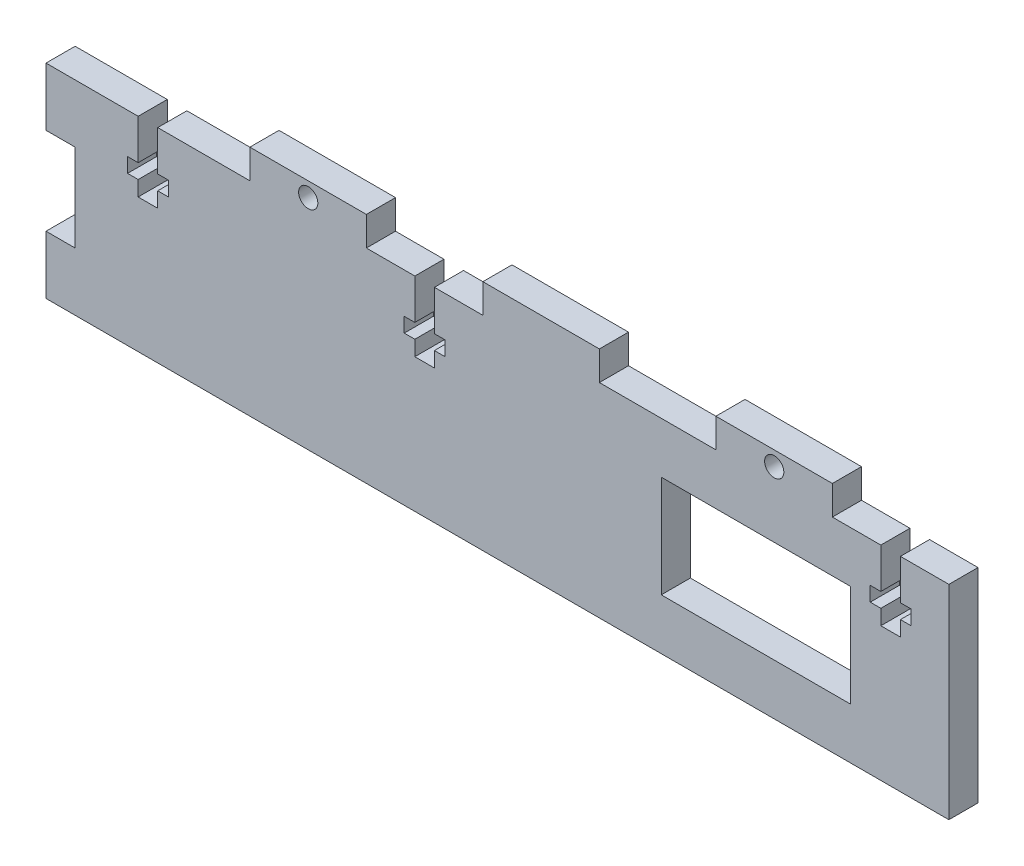
SolidWorks part; units mm, degrees
ref_plane "Front Plane" through (0, 0, 0) normal (0, 0, 1) x (1, 0, 0)
ref_plane "Top Plane" through (0, 0, 0) normal (0, 1, 0) x (1, 0, 0)
ref_plane "Right Plane" through (0, 0, 0) normal (1, 0, 0) x (0, 0, -1)
sketch "Sketch1" plane through (0, 0, 0) normal (0, 0, 1) x (1, 0, 0)
  line L0 (69.2576, 0) -> (-63.1151, 0) construction
  line L1 (42.067, 22.225) -> (-148.433, 22.225)
  line L2 (42.067, 22.225) -> (42.067, -22.225)
  line L3 (42.067, -22.225) -> (-148.433, -22.225)
  line L4 (-148.433, 22.225) -> (-148.433, -22.225)
  line L7 (25.98, 9.3599) -> (20.1295, 9.3599) construction
  line L8 (20.1295, -9.3599) -> (25.98, -9.3599) construction
  line L9 (-148.433, -69.85) -> (-148.433, 54.9538) construction
  line L10 (27.25, 6.27) -> (27.25, 8.0899) construction
  dimension "D1" = 44.45
  dimension "D2" = 14.817
extrude "Boss-Extrude1" add sketch "Sketch1" along normal blind 6.35
sketch "Sketch2" plane through (0, 0, 6.35) normal (0, 0, 1) x (1, 0, 0)
  line L0 (-43.1818, 0) -> (35.1848, 0) construction
  line L1 (-20.6375, 11.1125) -> (20.6375, 11.1125)
  line L2 (-20.6375, 11.1125) -> (-20.6375, -11.1125)
  line L3 (-20.6375, -11.1125) -> (20.6375, -11.1125)
  line L4 (20.6375, 11.1125) -> (20.6375, -11.1125)
  line L5 (-19.6295, 10.033) -> (19.6295, 10.033) construction
  line L6 (19.6295, -10.033) -> (-19.6295, -10.033) construction
  line L7 (0, 18.8234) -> (0, -13.1279) construction
  line L8 (-20.1295, -9.533) -> (-20.1295, 9.533) construction
  line L9 (20.1295, 9.533) -> (20.1295, -9.533) construction
  dimension "D1" = 22.225
  dimension "D2" = 41.275
extrude "Cut-Extrude1" cut sketch "Sketch2" against normal through all
sketch "Sketch3" plane through (0, 22.225, 0) normal (0, 1, 0) x (1, 0, 0)
  line L0 (16.667, 0) -> (16.667, -6.35)
  line L1 (42.067, 0) -> (-148.433, 0) construction
  line L2 (42.067, -6.35) -> (-148.433, -6.35) construction
  line L3 (16.667, -6.35) -> (-8.733, -6.35)
  line L4 (-8.733, -6.35) -> (-8.733, 0)
  line L5 (-8.733, 0) -> (16.667, 0)
  dimension "D1" = 25.4
  dimension "D2" = 25.4
extrude "Boss-Extrude2" add sketch "Sketch3" along normal blind 6.35
pattern_linear "LPattern1" count 3 spacing 50.8 along (-1, 0, 0) of "Boss-Extrude2"
sketch "Sketch4" plane through (-148.433, 0, 0) normal (-1, 0, 0) x (0, 0, 1)
  line L0 (6.35, 22.225) -> (6.35, 9.525)
  line L1 (6.35, 22.225) -> (6.35, -22.225) construction
  line L2 (6.35, 9.525) -> (0, 9.525)
  line L3 (0, 22.225) -> (0, -22.225) construction
  line L4 (0, 9.525) -> (0, 22.225)
  line L5 (0, 22.225) -> (6.35, 22.225)
  dimension "D1" = 12.7
extrude "Boss-Extrude3" add sketch "Sketch4" along normal blind 6.35
pattern_linear "LPattern2" count 2 spacing 31.75 along (0, -1, 0) of "Boss-Extrude3"
sketch "Sketch5" plane through (0, 0, 6.35) normal (0, 0, 1) x (1, 0, 0)
  line L0 (42.067, 22.225) -> (16.667, 22.225) construction
  line L1 (29.367, 22.225) -> (29.367, -8.4837) construction
  line L2 (42.067, 22.225) -> (16.667, 22.225) construction
  line L3 (-72.233, 22.225) -> (-72.233, 3.5007) construction
  line L4 (-59.533, 22.225) -> (-84.933, 22.225) construction
  line L5 (-132.558, 22.225) -> (-132.558, 4.6588) construction
  line L6 (-110.333, 22.225) -> (-154.783, 22.225) construction
  line L7 (-110.2918, 22.225) -> (-148.433, 22.225) construction
  line B0 (31.5006, 22.225) -> (27.2334, 22.225)
  line B1 (27.2334, 10.287) -> (24.922, 10.287)
  line B2 (24.922, 10.287) -> (24.922, 13.462)
  line B3 (24.922, 13.462) -> (27.2334, 13.462)
  line B4 (27.2334, 13.462) -> (27.2334, 22.225)
  line B5 (27.2334, 10.287) -> (27.2334, 6.985)
  line B6 (27.2334, 6.985) -> (31.5006, 6.985)
  line B7 (31.5006, 10.287) -> (31.5006, 6.985)
  line B8 (31.5006, 13.462) -> (31.5006, 22.225)
  line B9 (33.812, 13.462) -> (31.5006, 13.462)
  line B10 (33.812, 10.287) -> (33.812, 13.462)
  line B11 (31.5006, 10.287) -> (33.812, 10.287)
  line B12 (-70.0994, 22.225) -> (-74.3666, 22.225)
  line B13 (-74.3666, 10.287) -> (-76.678, 10.287)
  line B14 (-76.678, 10.287) -> (-76.678, 13.462)
  line B15 (-76.678, 13.462) -> (-74.3666, 13.462)
  line B16 (-74.3666, 13.462) -> (-74.3666, 22.225)
  line B17 (-74.3666, 10.287) -> (-74.3666, 6.985)
  line B18 (-74.3666, 6.985) -> (-70.0994, 6.985)
  line B19 (-70.0994, 10.287) -> (-70.0994, 6.985)
  line B20 (-70.0994, 13.462) -> (-70.0994, 22.225)
  line B21 (-67.788, 13.462) -> (-70.0994, 13.462)
  line B22 (-67.788, 10.287) -> (-67.788, 13.462)
  line B23 (-70.0994, 10.287) -> (-67.788, 10.287)
  line B24 (-130.4244, 22.225) -> (-134.6916, 22.225)
  line B25 (-134.6916, 10.287) -> (-137.003, 10.287)
  line B26 (-137.003, 10.287) -> (-137.003, 13.462)
  line B27 (-137.003, 13.462) -> (-134.6916, 13.462)
  line B28 (-134.6916, 13.462) -> (-134.6916, 22.225)
  line B29 (-134.6916, 10.287) -> (-134.6916, 6.985)
  line B30 (-134.6916, 6.985) -> (-130.4244, 6.985)
  line B31 (-130.4244, 10.287) -> (-130.4244, 6.985)
  line B32 (-130.4244, 13.462) -> (-130.4244, 22.225)
  line B33 (-128.113, 13.462) -> (-130.4244, 13.462)
  line B34 (-128.113, 10.287) -> (-128.113, 13.462)
  line B35 (-130.4244, 10.287) -> (-128.113, 10.287)
sketch_block_instance "TSlot-1"
sketch_block "TSlot" parameters "D1"=3.302, "D2"=3.175
sketch_block_instance "TSlot-4"
sketch_block_instance "TSlot-5"
extrude "Cut-Extrude2" cut sketch "Sketch5" against normal blind 6.35
sketch "Sketch6" plane through (0, 0, 0) normal (0, 0, -1) x (-1, 0, 0)
  line L0 (-1.854, 28.575) -> (-6.1212, 22.225) construction
  line L1 (-16.667, 28.575) -> (8.733, 28.575) construction
  line L2 (-1.854, 28.575) -> (-1.854, 22.225) construction
  line L3 (-6.1212, 28.575) -> (-1.854, 22.225) construction
  line L4 (-6.1212, 22.225) -> (-6.1212, 28.575) construction
  line L5 (99.746, 28.575) -> (95.4788, 22.225) construction
  line L6 (84.933, 28.575) -> (110.333, 28.575) construction
  line L7 (99.746, 28.575) -> (99.746, 22.225) construction
  line L8 (95.4788, 28.575) -> (99.746, 22.225) construction
  line L9 (95.4788, 22.225) -> (95.4788, 28.575) construction
  circle A0 centre (-3.9876, 25.4) radius 2.0955
  circle A1 centre (97.6124, 25.4) radius 2.0955
  dimension "D1" = 4.191
extrude "Cut-Extrude3" cut sketch "Sketch6" against normal through all
